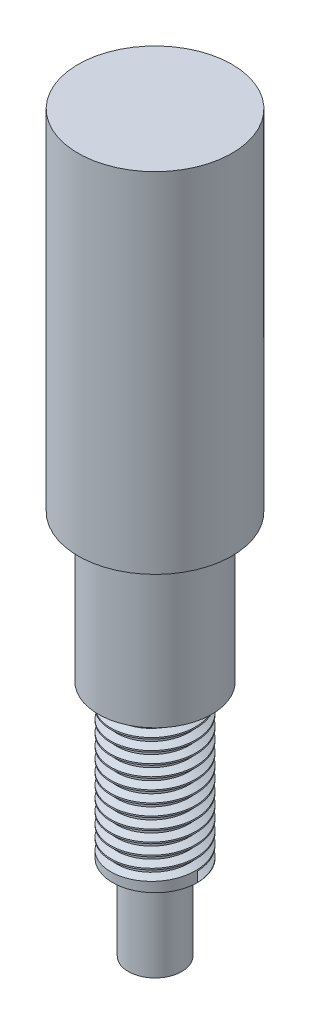
SolidWorks part; units mm, degrees
material "AISI 316 Annealed Stainless Steel Bar (SS)"
ref_plane "Front Plane" through (0, 0, 0) normal (0, 0, 1) x (1, 0, 0)
ref_plane "Top Plane" through (0, 0, 0) normal (0, 1, 0) x (1, 0, 0)
ref_plane "Right Plane" through (0, 0, 0) normal (1, 0, 0) x (0, 0, -1)
sketch "Sketch2" plane through (0, 0, 0) normal (0, 0, 1) x (1, 0, 0)
  line L0 (0, 0) -> (0, 508.8276) construction
  line L1 (0, 0) -> (6, 0)
  line L2 (0, 0) -> (0, 19.05)
  line L3 (0, 19.05) -> (6, 19.05)
  line L4 (6, 0) -> (6, 19.05)
  line L5 (0, 19.05) -> (9.525, 19.05)
  line L6 (0, 19.05) -> (0, 53.34)
  line L7 (0, 53.34) -> (9.525, 53.34)
  line L8 (9.525, 19.05) -> (9.525, 53.34)
  line L9 (0, 53.34) -> (12.721, 53.34)
  line L10 (0, 53.34) -> (0, 86.36)
  line L11 (0, 86.36) -> (12.721, 86.36)
  line L12 (12.721, 53.34) -> (12.721, 86.36)
  line L13 (0, 86.36) -> (17.272, 86.36)
  line L14 (0, 86.36) -> (0, 164.592)
  line L15 (0, 164.592) -> (17.272, 164.592)
  line L16 (17.272, 86.36) -> (17.272, 164.592)
  dimension "D1" = 78.232
  dimension "D2" = 17.272
  dimension "D4" = 33.02
  dimension "D3" = 12.721
  dimension "D5" = 34.29
  dimension "D6" = 9.525
  dimension "D7" = 19.05
  dimension "D8" = 6
revolve "Revolve1" add sketch "Sketch2" angle 360 about L0 region at (3, 9.525, 0) region at (4.7625, 36.195, 0) region at (6.3605, 69.85, 0) region at (8.636, 125.476, 0)
thread "Thread2" pitch 2.54 method cut profile "Thread Profile3" start angle 0, offset 0, length 0, pitch 2.54, diameter 19.05
ref_plane "Plane3" through (9.525, 19.05, 0) normal (0, 0, 1) x (1, 0, 0)
sketch "Thread Profile3" plane through (9.525, 19.05, 0) normal (0, 0, 1) x (1, 0, 0)
  line L0 (0, 0) -> (0, 2.54) construction
  line L11 (0, 0) -> (0, 2.2225)
  line L12 (0, 2.2225) -> (-1.3748, 1.4287)
  line L13 (-1.3748, 1.4287) -> (-1.3748, 0.7937)
  line L15 (-1.3748, 0.7937) -> (0, 0)
  line L17 (-1.3748, 1.1112) -> (0, 1.1112) construction
  point P2 (0, 0)
  dimension "Pitch" = 2.54
  dimension "Profile_Angle" = 60
  dimension "Profile_Land" = 0.635
  dimension "Profile_Height" = 1.3748
equation "\"hole diamiter\"= 1.36in"
equation "\"wheel depth\"= 2.88"
equation "\"press_tolerance\"= 0.00165"
equation "\"wheel_connection\"= \"hole diamiter\"'https://at-machining.com/tolerance-press-fit/"
equation "\"D1@Sketch2\"=\"wheel depth\"+0.2"
equation "\"D2@Sketch2\"=\"wheel_connection\"/2"
equation "\"fitting depth\"= 1.3"
equation "\"D4@Sketch2\"=\"fitting depth\""
equation "\"bearing_id\"= 1"
equation "\"bearing_connection\"= \"bearing_id\" + \"press_tolerance\"'https://at-machining.com/tolerance-press-fit/"
equation "\"D3@Sketch2\"=\"bearing_connection\"/2"
equation "\"thread length\"= 1.35"
equation "\"major_diamiter\"= 0.75 'https://www.machiningdoctor.com/threadinfo/?tid=81"
equation "\"D5@Sketch2\"=\"thread length\""
equation "\"D6@Sketch2\"=\"major_diamiter\"/2"
equation "\"coupling diamiter\"= 12mm"
equation "\"coupling lenght\"= 1.5 / 2"
equation "\"D7@Sketch2\"=\"coupling lenght\""
equation "\"D8@Sketch2\"=\"coupling diamiter\"/2"
